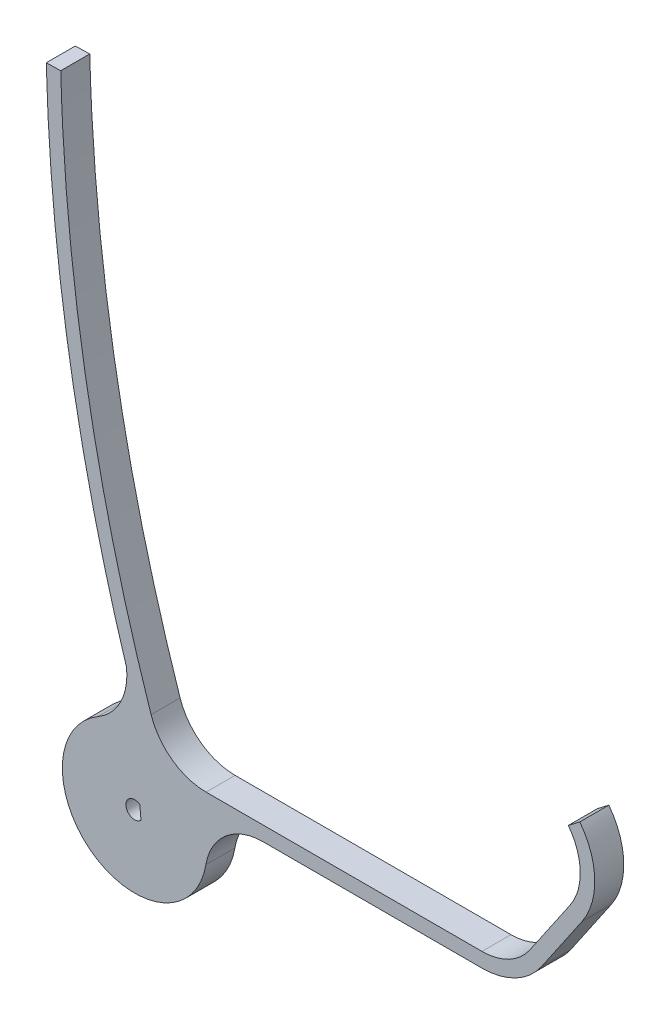
SolidWorks part; units mm, degrees
ref_plane "Front Plane" through (0, 0, 0) normal (0, 0, 1) x (1, 0, 0)
ref_plane "Top Plane" through (0, 0, 0) normal (0, 1, 0) x (1, 0, 0)
ref_plane "Right Plane" through (0, 0, 0) normal (1, 0, 0) x (0, 0, -1)
sketch "Sketch1" plane through (0, 0, 0) normal (0, 0, 1) x (1, 0, 0)
  line L0 (41.9192, -40.4755) -> (34.9778, -50.6396) construction
  line L1 (26.7198, -55) -> (-20.8371, -55) construction
  line L2 (41.9192, -40.4755) -> (34.9778, -50.6396)
  line L3 (26.7198, -55) -> (-20.8371, -55)
  line L4 (26.7198, -57.5) -> (-11.0053, -57.5)
  line L5 (43.9837, -41.8854) -> (37.0423, -52.0495)
  line L6 (-45.89, 40.1717) -> (-48.3891, 40.1055)
  line L7 (43.5849, -27.2352) -> (41.6001, -28.7554)
  line L8 (-29.4878, -65.3726) -> (-29.8605, -61.5176)
  line L9 (-32.0549, -64.7985) -> (-32.2702, -62.5728)
  line L10 (-32.0549, -64.7985) -> (-32.2702, -62.5728)
  line L11 (26.7198, -57.5) -> (-20.8371, -57.5) construction
  arc A0 (41.9192, -40.4755) -> (41.6001, -28.7554) centre (33.6612, -34.8359) ccw construction
  arc A1 (26.7198, -55) -> (34.9778, -50.6396) centre (26.7198, -45) ccw construction
  arc A2 (-30.3198, -48.1747) -> (-20.8371, -55) centre (-20.8371, -45) ccw construction
  arc A3 (41.9192, -40.4755) -> (41.6001, -28.7554) centre (33.6612, -34.8359) ccw
  arc A4 (26.7198, -55) -> (34.9778, -50.6396) centre (26.7198, -45) ccw
  arc A5 (-30.3198, -48.1747) -> (-20.8371, -55) centre (-20.8371, -45) ccw
  arc A7 (26.7198, -57.5) -> (37.0423, -52.0495) centre (26.7198, -45) ccw
  arc A8 (43.9837, -41.8854) -> (43.5849, -27.2352) centre (33.6612, -34.8359) ccw
  arc A9 (-39.4468, -53.0227) -> (-20.8673, -65.8448) centre (-33.1579, -63.7819) ccw
  arc A10 (-39.4468, -53.0227) -> (-34.5672, -43.1743) centre (-44.4932, -44.3893) ccw
  arc A11 (-32.2702, -62.5728) -> (-34.6509, -63.9263) centre (-33.1579, -63.7819) ccw
  arc A12 (-34.6509, -63.9263) -> (-32.0549, -64.7985) centre (-33.1579, -63.7819) ccw
  arc A13 (-32.2702, -62.5728) -> (-34.6509, -63.9263) centre (-33.1579, -63.7819) ccw
  arc A14 (-34.6509, -63.9263) -> (-32.0549, -64.7985) centre (-33.1579, -63.7819) ccw
  arc A15 (-20.8673, -65.8448) -> (-11.0053, -57.5) centre (-11.0053, -67.5) cw
  arc A18 (-29.8605, -61.5176) -> (-37.1393, -64.1669) centre (-33.1579, -63.7819) ccw
  arc A19 (-32.6905, -48.9684) -> (-20.8371, -57.5) centre (-20.8371, -45) ccw construction
  arc A20 (-37.1393, -64.1669) -> (-29.4878, -65.3726) centre (-33.1579, -63.7819) ccw
  parabola Q0 (-30.3198, -48.1747) -> (-45.89, 40.1717) focus (106.8057, 19.2248) apex (-40.5899, -9.0139) construction
  parabola Q1 (-30.3198, -48.1747) -> (-45.89, 40.1717) focus (106.8057, 19.2248) apex (-40.5899, -9.0139)
  spline S0 degree 1 poles (-32.6905, -48.9684) (-48.3891, 40.1055) knots 0 0 1 1 construction
  spline S1 degree 3 poles (-48.3891, 40.1055) (-48.2883, 36.2995) (-47.9475, 28.6772) (-46.7138, 13.5748) (-44.1346, -5.119) (-40.1715, -23.5474) (-36.8423, -35.6875) (-35.0956, -41.4908) (-33.9628, -45.1092) (-33.1734, -47.526) (-32.6905, -48.9684) knots 0.499176 0.499176 0.499176 0.499176 0.499404 0.499633 0.500091 0.500549 0.500777 0.500853 0.500914 0.501006 0.501006 0.501006 0.501006 only from (-48.3891, 40.1055) to (-34.5672, -43.1743)
  point P24 (-34.6509, -43.2005)
  point P36 (-9.2758, -69.6237)
  point P37 (-52.884, -41.8854)
  point P38 (0, 0)
  dimension "D3" = 10
  dimension "D4" = 10
  dimension "D1" = 2.5
  dimension "D2" = 0
  dimension "D5" = 2.5
extrude "Boss-Extrude1" add sketch "Sketch1" against normal blind 5 contours L6 S1 A10 A9 A15 L4 A7 L5 A8 L7 A3 L2 A4 L3 A5 Q1 A20 A18 L8 region at (45.1566, -34.523, 0)
extrude "Boss-Extrude2" add sketch "Sketch1<3>" against normal blind 7.5 contours A18 A20 L8 A14 A13 L10 region at (-33.7632, -67.6237, 0)
sketch "Sketch1<3>" plane through (0, 0, 0) normal (0, 0, 1) x (1, 0, 0) same geometry as "Sketch1"
fillet "Fillet1" radius 5 1 edges at (-37.1393, -64.1669, -5)
fillet "Fillet2" radius 5 1 edges at (-29.6741, -63.4451, -5)
